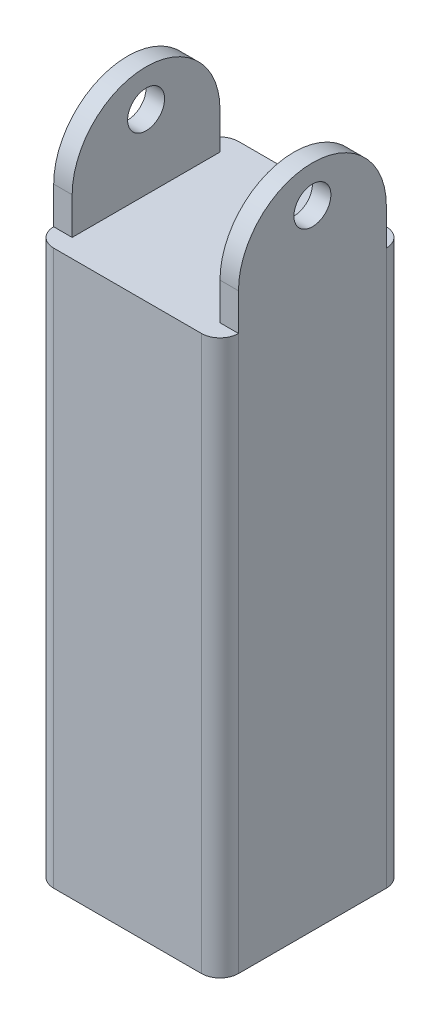
SolidWorks part; units mm, degrees
material "Mahogany"
ref_plane "Front Plane" through (0, 0, 0) normal (0, 0, 1) x (1, 0, 0)
ref_plane "Top Plane" through (0, 0, 0) normal (0, 1, 0) x (1, 0, 0)
ref_plane "Right Plane" through (0, 0, 0) normal (1, 0, 0) x (0, 0, -1)
sketch "Sketch1" plane through (0, 0, 0) normal (0, 1, 0) x (1, 0, 0)
  line L1 (-50, 50) -> (50, 50)
  line L2 (-50, 50) -> (-50, -50)
  line L3 (-50, -50) -> (50, -50)
  line L4 (50, 50) -> (50, -50)
  line L5 (-50, 50) -> (50, -50) construction
  line L6 (-50, -50) -> (50, 50) construction
  point P0 (0, 0)
  dimension "D1" = 100
  dimension "D2" = 100
extrude "Boss-Extrude1" add sketch "Sketch1" along normal blind 300
fillet "Fillet1" radius 10 4 edges at (-50, 150, 50) (-50, 150, -50) (50, 150, -50) (50, 150, 50)
sketch "Sketch2" plane through (0, 300, 0) normal (0, 1, 0) x (1, 0, 0)
  point P0 (0, 0)
sketch "Sketch4" plane through (0, 300, 0) normal (0, 1, 0) x (1, 0, 0)
  line L0 (-40, -50) -> (40, -50) construction
  point P0 (0, -50)
  point P4 (0, 0)
ref_plane "Plane1" through (50, 0, 0) normal (1, 0, 0) x (0, 0, -1)
sketch "Sketch5" plane through (50, 0, 0) normal (1, 0, 0) x (0, 0, -1)
  line L0 (40, 300) -> (-40, 300)
  line L1 (-40, 300) -> (-40, 360)
  line L2 (-40, 360) -> (40, 360)
  line L3 (40, 360) -> (40, 300)
  circle A0 centre (0, 340) radius 10
  dimension "D2" = 20
  dimension "D1" = 60
  dimension "D3" = 20
  dimension "D4" = 40
extrude "Boss-Extrude2" add sketch "Sketch5" against normal blind 10
fillet "Fillet2" 2 edges at (45, 360, 40) (45, 360, -40) type full round first side face at (45, 330, 40) second side face at (45, 330, -40) middle face at (45, 360, 0)
mirror "Mirror1" about plane through (0, 0, 0) normal (1, 0, 0) of "Fillet2", "Boss-Extrude2"
